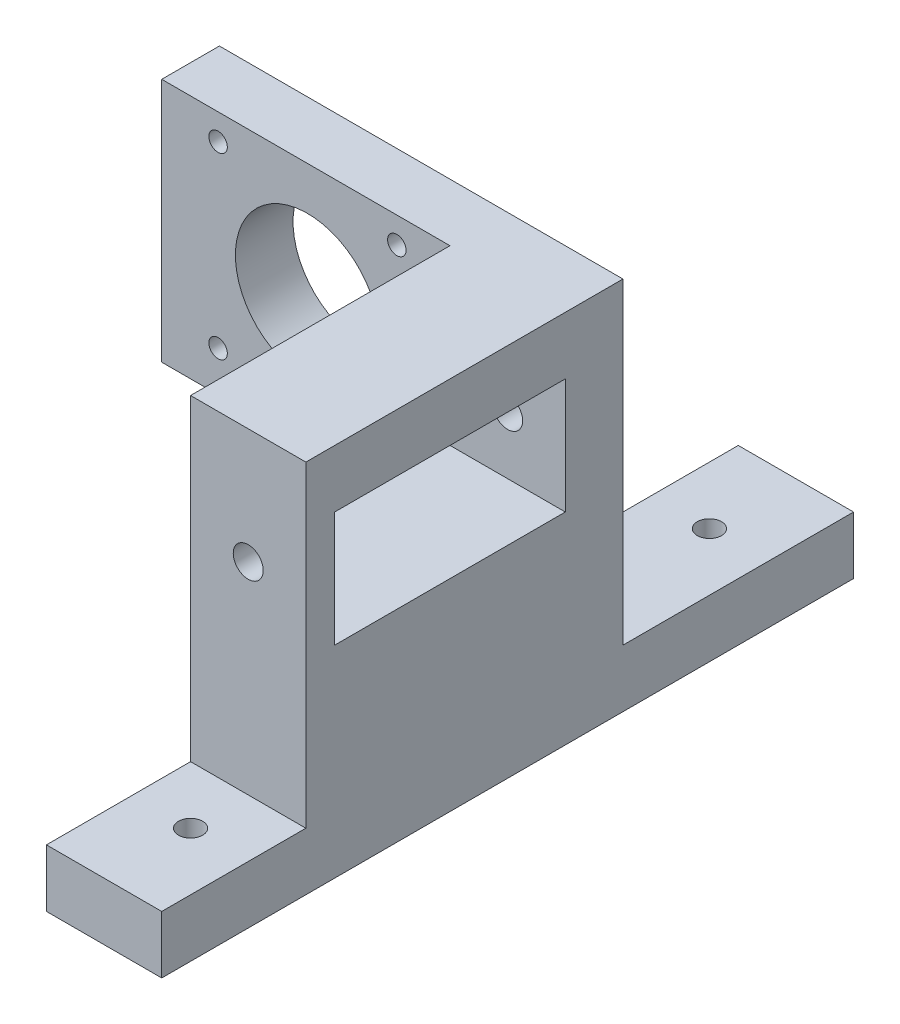
SolidWorks part; units mm, degrees
ref_plane "Front Plane" through (0, 0, 0) normal (0, 0, 1) x (1, 0, 0)
ref_plane "Top Plane" through (0, 0, 0) normal (0, 1, 0) x (1, 0, 0)
ref_plane "Right Plane" through (0, 0, 0) normal (1, 0, 0) x (0, 0, -1)
sketch "Sketch4" plane through (0, 0, 0) normal (0, 1, 0) x (1, 0, 0)
  line L1 (0, 0) -> (20, 0)
  line L2 (0, 0) -> (0, 120)
  line L3 (0, 120) -> (20, 120)
  line L4 (20, 0) -> (20, 120)
  dimension "D1" = 120
  dimension "D2" = 20
extrude "Boss-Extrude4" add sketch "Sketch4" along normal blind 10
sketch "Sketch5" plane through (0, 10, 0) normal (0, 1, 0) x (1, 0, 0)
  line L0 (10, 0) -> (10, 15) construction
  line L1 (0, 0) -> (20, 0) construction
  line L2 (10, 120) -> (10, 105) construction
  line L3 (20, 120) -> (0, 120) construction
  circle A0 centre (10, 105) radius 2.1
  circle A1 centre (10, 15) radius 2.1
  dimension "D3" = 4.2
  dimension "D4" = 4.2
  dimension "D1" = 15
  dimension "D2" = 15
extrude "Cut-Extrude1" cut sketch "Sketch5" against normal blind 10
sketch "Sketch8" plane through (0, 10, 0) normal (0, 1, 0) x (1, 0, 0)
  line L0 (20, 0) -> (20, 120) construction
  line L1 (20, 25) -> (0, 25)
  line L2 (20, 25) -> (20, 80)
  line L3 (20, 80) -> (0, 80)
  line L4 (0, 25) -> (0, 80)
  line L5 (0, 0) -> (20, 0) construction
  point P6 (0, 0)
  dimension "D1" = 55
  dimension "D2" = 20
  dimension "D3" = 25
extrude "Boss-Extrude6" add sketch "Sketch8" along normal blind 55
sketch "Sketch9" plane through (0, 0, 0) normal (-1, 0, 0) x (0, 0, 1)
  line L0 (-80, 65) -> (-80, 10) construction
  line L5 (-70, 55) -> (-30, 55)
  line L6 (-70, 55) -> (-70, 35)
  line L7 (-70, 35) -> (-30, 35)
  line L8 (-30, 55) -> (-30, 35)
  line L9 (-80, 65) -> (-25, 65) construction
  dimension "D1" = 20
  dimension "D2" = 40
  dimension "D3" = 10
  dimension "D4" = 10
extrude "Cut-Extrude2" cut sketch "Sketch9" against normal blind 20
sketch "Sketch11" plane through (0, 0, -70) normal (0, 0, 1) x (1, 0, 0)
  line L0 (0, 45) -> (20, 45)
  line L1 (0, 55) -> (0, 35) construction
  line L2 (20, 55) -> (20, 35) construction
  circle A0 centre (10, 45) radius 2.6
  dimension "D1" = 5.2
extrude "Cut-Extrude3" cut sketch "Sketch11" against normal mid plane 100 contours A0
sketch "Sketch12" plane through (0, 0, 0) normal (-1, 0, 0) x (0, 0, 1)
  line L1 (-80, 65) -> (-70, 65)
  line L2 (-80, 65) -> (-80, 10)
  line L3 (-80, 10) -> (-70, 10)
  line L4 (-70, 65) -> (-70, 10)
  dimension "D1" = 55
  dimension "D2" = 10
extrude "Boss-Extrude7" add sketch "Sketch12" along normal blind 50
sketch "Sketch15" plane through (0, 0, -70) normal (0, 0, 1) x (1, 0, 0)
  line L0 (0, 65) -> (20, 65) construction
  line L1 (-40.2253, 60.5002) -> (-9.2253, 60.5002)
  line L2 (-40.2253, 60.5002) -> (-40.2253, 29.5002)
  line L3 (-40.2253, 29.5002) -> (-9.2253, 29.5002)
  line L4 (-9.2253, 60.5002) -> (-9.2253, 29.5002)
  line L5 (-40.2253, 60.5002) -> (-9.2253, 29.5002) construction
  line L6 (-40.2253, 29.5002) -> (-9.2253, 60.5002) construction
  line L7 (-50, 10) -> (-50, 65) construction
  line L8 (-50, 65) -> (0, 65) construction
  circle A0 centre (-24.7253, 45.0002) radius 12.5
  circle A1 centre (-9.2253, 60.5002) radius 1.6
  circle A2 centre (-9.2253, 29.5002) radius 1.6
  circle A3 centre (-40.2253, 29.5002) radius 1.6
  circle A4 centre (-40.2253, 60.5002) radius 1.6
  point P19 (-24.7253, 45.0002)
  dimension "D1" = 25
  dimension "D6" = 3.2
  dimension "D2" = 31
  dimension "D3" = 19.9998
  dimension "D4" = 9.7747
  dimension "D5" = 4.4998
extrude "Cut-Extrude4" cut sketch "Sketch15" against normal up to surface (10 mm away) contours A0 | L4 A1 L1 | L1 A1 L4 | L3 A2 L4 | L4 A2 L3 | L2 A3 L3 | L3 A3 L2 | L2 A4 L1 | L1 A4 L2 region at (-40.4516, 60.7266, -70) region at (-39.5462, 59.8212, -70) region at (-8.9989, 60.7266, -70) region at (-9.9043, 59.8212, -70) region at (-39.5462, 30.1793, -70) region at (-40.4516, 29.2739, -70) region at (-8.9989, 29.2739, -70) region at (-9.9043, 30.1793, -70) region at (-24.7253, 45.0002, -70) up to face at (12.6, 45, -80)
sketch "Sketch17" plane through (0, 0, -70) normal (0, 0, 1) x (1, 0, 0)
  line L1 (-50, 10) -> (0, 10)
  line L2 (-50, 10) -> (-50, 22.5)
  line L3 (-50, 22.5) -> (0, 22.5)
  line L4 (0, 10) -> (0, 22.5)
  line L5 (0, 10) -> (0, 35) construction
  dimension "D1" = 12.5
  dimension "D2" = 50
extrude "Cut-Extrude6" cut sketch "Sketch17" against normal up to surface (10 mm away) contours L2 L1 L4 L3 up to face at (-38.6253, 60.5002, -80)
chamfer "Chamfer1" distance 12.5 angle 45 1 edges at (0, 22.5, -75)
